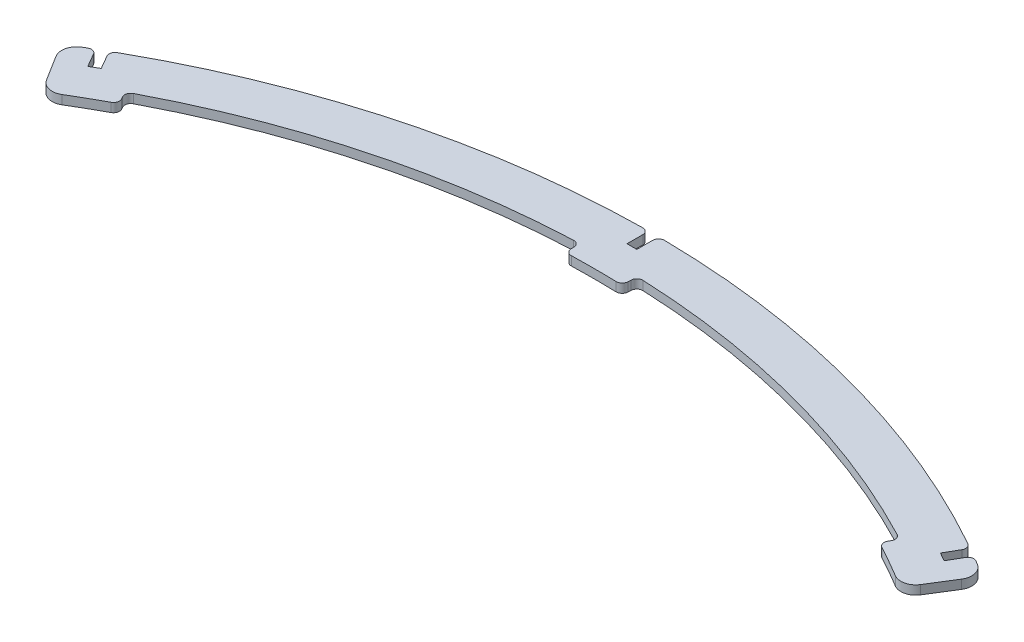
SolidWorks part; units mm, degrees
ref_plane "Front Plane" through (0, 0, 0) normal (0, 0, 1) x (1, 0, 0)
ref_plane "Top Plane" through (0, 0, 0) normal (0, 1, 0) x (1, 0, 0)
ref_plane "Right Plane" through (0, 0, 0) normal (1, 0, 0) x (0, 0, -1)
sketch "Sketch1" plane through (0, 0, 0) normal (0, 1, 0) x (1, 0, 0)
  line L0 (0, 0) -> (0, 291.5) construction
  line L1 (-145.75, 252.4464) -> (0, 0) construction
  line L2 (0, 0) -> (145.75, 252.4464) construction
  line L3 (-147.1766, 251.6174) -> (-143.5289, 245.2994)
  line L4 (-143.5289, 245.2994) -> (-140.6711, 246.9494)
  line L5 (-140.6711, 246.9494) -> (-144.3187, 253.2674)
  line L6 (-1.65, 291.4953) -> (-1.65, 284.2)
  line L7 (1.65, 284.2) -> (1.65, 291.4953)
  line L8 (-1.65, 284.2) -> (1.65, 284.2)
  line L9 (144.3187, 253.2674) -> (140.6711, 246.9494)
  line L10 (143.5289, 245.2994) -> (147.1766, 251.6174)
  line L11 (140.6711, 246.9494) -> (143.5289, 245.2994)
  line L12 (-154.4715, 247.206) -> (-143.8731, 230.2451)
  line L13 (-127.4615, 239.7203) -> (-129.8089, 244.135)
  line L14 (154.4715, 247.206) -> (143.8731, 230.2451)
  line L15 (127.4615, 239.7203) -> (129.8089, 244.135)
  line L16 (9.4752, 271.3346) -> (9.6497, 276.3316)
  line L17 (-9.6497, 276.3316) -> (-9.4752, 271.3346)
  circle A0 centre (0, 0) radius 291.5 construction
  circle A1 centre (0, 0) radius 284.5 construction
  arc A2 (1.65, 291.4953) -> (144.3187, 253.2674) centre (0, 0) cw
  arc A3 (-144.3187, 253.2674) -> (-1.65, 291.4953) centre (0, 0) cw
  arc A4 (-129.8089, 244.135) -> (-9.6497, 276.3316) centre (0, 0) cw
  arc A5 (-147.1766, 251.6174) -> (-154.4715, 247.206) centre (0, 0) ccw
  arc A6 (147.1766, 251.6174) -> (154.4715, 247.206) centre (0, 0) cw
  arc A7 (-143.8731, 230.2451) -> (-127.4615, 239.7203) centre (0, 0) cw
  arc A8 (143.8731, 230.2451) -> (127.4615, 239.7203) centre (0, 0) ccw
  arc A9 (-9.4752, 271.3346) -> (9.4752, 271.3346) centre (0, 0) cw
  arc A10 (9.6497, 276.3316) -> (129.8089, 244.135) centre (0, 0) cw
  point P12 (-142.25, 246.3842)
  point P23 (0, 0)
  point P41 (0, 0)
  dimension "D1" = 583
  dimension "D2" = 569
  dimension "D3" = 30
  dimension "D4" = 30
  dimension "D5" = 0.3
  dimension "D6" = 1.65
  dimension "D7" = 1.65
  dimension "D9" = 15
  dimension "D10" = 2
  dimension "D11" = 20
  dimension "D12" = 2
  dimension "D8" = 3
  dimension "D13" = 2
extrude "Boss-Extrude1" add sketch "Sketch1" along normal blind 3
fillet "Fillet1" radius 2 8 edges at (127.4615, 1.5, -239.7203) (129.8089, 1.5, -244.135) (-127.4615, 1.5, -239.7203) (-129.8089, 1.5, -244.135) (-9.6497, 1.5, -276.3316) (-9.4752, 1.5, -271.3346) (9.4752, 1.5, -271.3346) (9.6497, 1.5, -276.3316)
fillet "Fillet2" radius 5 4 edges at (-154.4715, 1.5, -247.206) (-143.8731, 1.5, -230.2451) (154.4715, 1.5, -247.206) (143.8731, 1.5, -230.2451)
fillet "Fillet3" radius 2 6 edges at (147.1766, 1.5, -251.6174) (144.3187, 1.5, -253.2674) (-1.65, 1.5, -291.4953) (1.65, 1.5, -291.4953) (-144.3187, 1.5, -253.2674) (-147.1766, 1.5, -251.6174)
equation "\"D4@Sketch1\"=\"D3@Sketch1\""
equation "\"D7@Sketch1\"=\"D6@Sketch1\""
